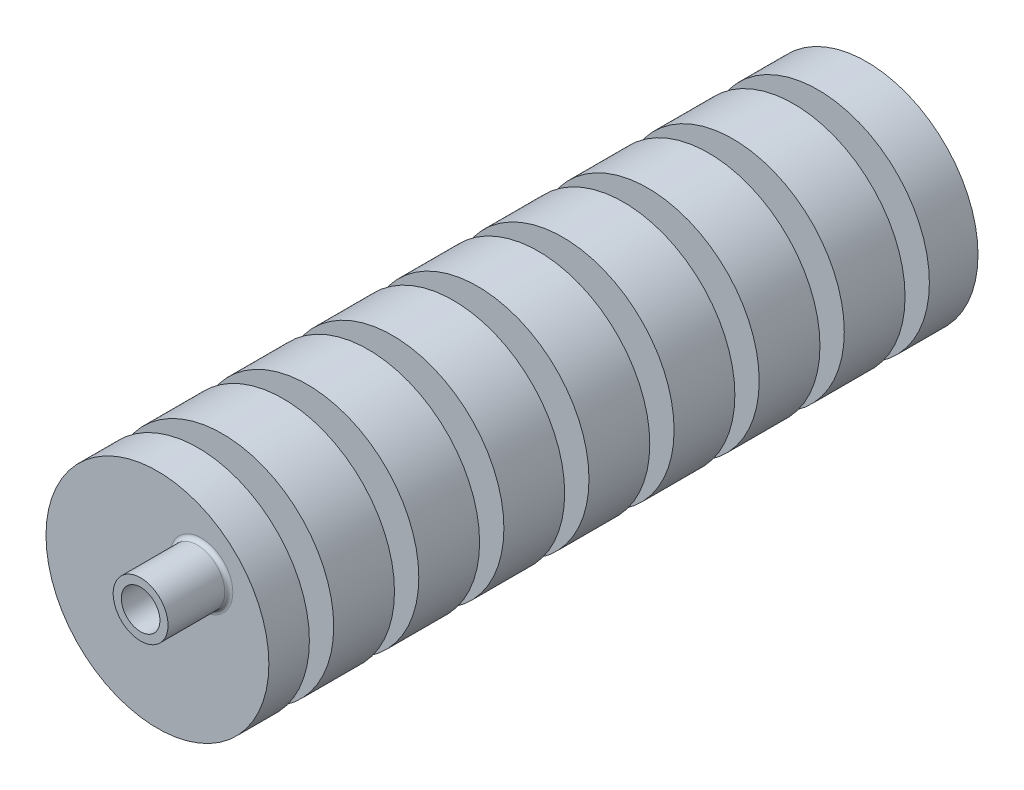
SolidWorks part; units mm, degrees
material "RUBBER 65A"
ref_plane "Front Plane" through (0, 0, 0) normal (0, 0, 1) x (1, 0, 0)
ref_plane "Top Plane" through (0, 0, 0) normal (0, 1, 0) x (1, 0, 0)
ref_plane "Right Plane" through (0, 0, 0) normal (1, 0, 0) x (0, 0, -1)
sketch "Sketch3" plane through (0, 0, 0) normal (0, 0, 1) x (1, 0, 0)
  circle A0 centre (0, 0) radius 27.5
  dimension "D1" = 55
extrude "Boss-Extrude2" add sketch "Sketch3" along normal blind 175
ref_axis "Axis2" through (0, 0, 174.1287) along (0, 0, -1)
sketch "Sketch5" plane through (0, 0, 175) normal (0, 0, 1) x (1, 0, 0)
  circle A0 centre (0, 0) radius 3.175
  dimension "D1" = 6.35
extrude "Cut-Extrude1" cut sketch "Sketch5" against normal through all contours A0
sketch "Sketch4" plane through (0, 0, 0) normal (0, 1, 0) x (1, 0, 0)
  line L0 (0, -175) -> (0, 0) construction
  line L1 (-27.5, -175) -> (27.5, -175) construction
  line L3 (-27.5, -165) -> (-11.5, -165)
  line L4 (-27.5, -165) -> (-27.5, -159)
  line L5 (-27.5, -159) -> (-11.5, -159)
  line L6 (-11.5, -165) -> (-11.5, -159)
  line L63 (-27.5, -144) -> (-27.5, -138)
  line L64 (-27.5, -144) -> (-11.5, -144)
  line L65 (-11.5, -144) -> (-11.5, -138)
  line L66 (-27.5, -138) -> (-11.5, -138)
  line L67 (-27.5, -123) -> (-27.5, -117)
  line L68 (-27.5, -123) -> (-11.5, -123)
  line L69 (-11.5, -123) -> (-11.5, -117)
  line L70 (-27.5, -117) -> (-11.5, -117)
  line L71 (-27.5, -102) -> (-27.5, -96)
  line L72 (-27.5, -102) -> (-11.5, -102)
  line L73 (-11.5, -102) -> (-11.5, -96)
  line L74 (-27.5, -96) -> (-11.5, -96)
  line L75 (-27.5, -81) -> (-27.5, -75)
  line L76 (-27.5, -81) -> (-11.5, -81)
  line L77 (-11.5, -81) -> (-11.5, -75)
  line L78 (-27.5, -75) -> (-11.5, -75)
  line L79 (-27.5, -60) -> (-27.5, -54)
  line L80 (-27.5, -60) -> (-11.5, -60)
  line L81 (-11.5, -60) -> (-11.5, -54)
  line L82 (-27.5, -54) -> (-11.5, -54)
  line L83 (-27.5, -39) -> (-27.5, -33)
  line L84 (-27.5, -39) -> (-11.5, -39)
  line L85 (-11.5, -39) -> (-11.5, -33)
  line L86 (-27.5, -33) -> (-11.5, -33)
  line L87 (-27.5, -18) -> (-27.5, -12)
  line L88 (-27.5, -18) -> (-11.5, -18)
  line L89 (-11.5, -18) -> (-11.5, -12)
  line L90 (-27.5, -12) -> (-11.5, -12)
  line L91 (-27.5, -165) -> (-27.5, -144) construction
  dimension "D1" = 10
  dimension "D2" = 6
  dimension "D3" = 27.5
  dimension "D4" = 16
  dimension "D6" = 21
  dimension "D5" = 8
revolve "Cut-Revolve1" cut sketch "Sketch4" angle 360 about L0
shell "Shell1" thickness 3
sketch "Sketch10" plane through (0, 0, 0) normal (0, 0, -1) x (-1, 0, 0)
  line L0 (0, 27.5) -> (0, -27.5) construction
  line L1 (-27.5, 0) -> (27.5, 0) construction
  line L2 (-1, 27.4818) -> (-1, 3.0134)
  line L3 (1, 3.0134) -> (1, 27.4818)
  line L4 (3.0134, 1) -> (27.4818, 1)
  line L5 (3.0134, -1) -> (27.4818, -1)
  line L6 (-1, -3.0134) -> (-1, -27.4818)
  line L7 (1, -3.0134) -> (1, -27.4818)
  line L8 (-27.4818, -1) -> (-3.0134, -1)
  line L9 (-27.4818, 1) -> (-3.0134, 1)
  circle A0 centre (0, 0) radius 27.5 construction
  circle A1 centre (0, 0) radius 3.175 construction
  arc A2 (-1, -27.4818) -> (1, -27.4818) centre (0, 0) ccw
  arc A3 (27.4818, -1) -> (27.4818, 1) centre (0, 0) ccw
  arc A4 (1, 27.4818) -> (-1, 27.4818) centre (0, 0) ccw
  arc A5 (-27.4818, 1) -> (-27.4818, -1) centre (0, 0) ccw
  arc A6 (-1, -3.0134) -> (1, -3.0134) centre (0, 0) ccw
  arc A7 (-3.0134, 1) -> (-3.0134, -1) centre (0, 0) ccw
  arc A8 (1, 3.0134) -> (-1, 3.0134) centre (0, 0) ccw
  arc A9 (3.0134, -1) -> (3.0134, 1) centre (0, 0) ccw
  dimension "D1" = 1
  dimension "D2" = 1
  dimension "D3" = 1
  dimension "D4" = 1
  dimension "D5" = 1
extrude "Boss-Extrude3" add sketch "Sketch10" against normal up to surface (175 mm away) up to face at (3.175, 0, 175)
sketch "Sketch11" plane through (0, 0, 0) normal (1, 0, 0) x (0, 0, -1)
  line L0 (-117, 27.4818) -> (-117, 1) construction
  line L1 (-165, 30.0791) -> (-159, 30.0791)
  line L2 (-165, 30.0791) -> (-165, 11.4564)
  line L3 (-165, 11.4564) -> (-159, 11.4564)
  line L4 (-159, 30.0791) -> (-159, 11.4564)
  line L5 (-144, 30.0191) -> (-138, 30.0191)
  line L6 (-144, 30.0191) -> (-144, 11.4564)
  line L7 (-144, 11.4564) -> (-138, 11.4564)
  line L8 (-138, 30.0191) -> (-138, 11.4564)
  line L9 (-123, 30.1992) -> (-117, 30.1992)
  line L10 (-123, 30.1992) -> (-123, 11.4755)
  line L11 (-123, 11.4755) -> (-117, 11.4755)
  line L12 (-117, 30.1992) -> (-117, 11.4755)
  line L13 (-117, 11.4564) -> (-117, 1) construction
  line L14 (-75, 11.4564) -> (-75, 1) construction
  line L15 (-102, 30.5593) -> (-96, 30.5593)
  line L16 (-102, 30.5593) -> (-102, 11.4564)
  line L17 (-102, 11.4564) -> (-96, 11.4564)
  line L18 (-96, 30.5593) -> (-96, 11.4564)
  line L19 (-81, 30.9195) -> (-75, 30.9195)
  line L20 (-81, 30.9195) -> (-81, 11.4755)
  line L21 (-81, 11.4755) -> (-75, 11.4755)
  line L22 (-75, 30.9195) -> (-75, 11.4755)
  line L23 (-75, 27.4818) -> (-75, 1) construction
  line L25 (-60, 31.9241) -> (-54, 31.9241)
  line L26 (-60, 31.9241) -> (-60, 11.4564)
  line L27 (-60, 11.4564) -> (-54, 11.4564)
  line L28 (-54, 31.9241) -> (-54, 11.4564)
  line L29 (-39, 30.6232) -> (-33, 30.6232)
  line L30 (-39, 30.6232) -> (-39, 11.4564)
  line L31 (-39, 11.4564) -> (-33, 11.4564)
  line L32 (-33, 30.6232) -> (-33, 11.4564)
  line L33 (-18, 31.5847) -> (-12, 31.5847)
  line L34 (-18, 31.5847) -> (-18, 11.4564)
  line L35 (-18, 11.4564) -> (-12, 11.4564)
  line L36 (-12, 31.5847) -> (-12, 11.4564)
revolve "Cut-Revolve2" cut sketch "Sketch11" angle 360 about axis through (0, 0, 174.1287) along (0, 0, -1)
sketch "Sketch12" plane through (0, 0, 0) normal (0, 1, 0) x (1, 0, 0)
  line L0 (24.4796, -172) -> (6.0935, -172) construction
  line L1 (24.7296, -168) -> (23.4796, -168)
  line L2 (24.7296, -168) -> (24.7296, -172)
  line L3 (24.7296, -172) -> (23.4796, -172)
  line L4 (23.4796, -168) -> (23.4796, -172)
  line L5 (0, 0) -> (0, -175) construction
  line L6 (-3.175, -175) -> (3.175, -175) construction
  line L7 (24.4796, -156) -> (8.441, -156) construction
  line L8 (24.4796, -9) -> (8.441, -9) construction
  line L9 (24.7296, -3) -> (23.4796, -3)
  line L10 (24.7296, -3) -> (24.7296, -9)
  line L11 (24.7296, -9) -> (23.4796, -9)
  line L12 (23.4796, -3) -> (23.4796, -9)
  line L13 (24.7296, -147) -> (23.4796, -147)
  line L14 (24.7296, -147) -> (24.7296, -156)
  line L15 (24.7296, -156) -> (23.4796, -156)
  line L16 (23.4796, -147) -> (23.4796, -156)
  line L17 (24.4796, -135) -> (8.441, -135) construction
  line L18 (24.7296, -126) -> (23.4796, -126)
  line L19 (24.7296, -126) -> (24.7296, -135)
  line L20 (24.7296, -135) -> (23.4796, -135)
  line L21 (23.4796, -126) -> (23.4796, -135)
  line L22 (24.4796, -114) -> (8.441, -114) construction
  line L23 (24.7296, -105) -> (23.4796, -105)
  line L24 (24.7296, -105) -> (24.7296, -114)
  line L25 (24.7296, -114) -> (23.4796, -114)
  line L26 (23.4796, -105) -> (23.4796, -114)
  line L27 (24.4796, -93) -> (8.441, -93) construction
  line L28 (24.7296, -84) -> (23.4796, -84)
  line L29 (24.7296, -84) -> (24.7296, -93)
  line L30 (24.7296, -93) -> (23.4796, -93)
  line L31 (23.4796, -84) -> (23.4796, -93)
  line L32 (24.4796, -72) -> (8.441, -72) construction
  line L33 (24.7296, -63) -> (23.4796, -63)
  line L34 (24.7296, -63) -> (24.7296, -72)
  line L35 (24.7296, -72) -> (23.4796, -72)
  line L36 (23.4796, -63) -> (23.4796, -72)
  line L37 (24.4796, -51) -> (8.441, -51) construction
  line L38 (24.7296, -42) -> (23.4796, -42)
  line L39 (24.7296, -42) -> (24.7296, -51)
  line L40 (24.7296, -51) -> (23.4796, -51)
  line L41 (23.4796, -42) -> (23.4796, -51)
  line L42 (24.4796, -30) -> (8.441, -30) construction
  line L43 (24.7296, -21) -> (23.4796, -21)
  line L44 (24.7296, -21) -> (24.7296, -30)
  line L45 (24.7296, -30) -> (23.4796, -30)
  line L46 (23.4796, -21) -> (23.4796, -30)
  dimension "D1" = 1.25
  dimension "D2" = 1.25
  dimension "D3" = 1.25
  dimension "D4" = 1.25
  dimension "D5" = 1.25
  dimension "D6" = 1.25
  dimension "D7" = 1.25
  dimension "D8" = 1.25
  dimension "D9" = 1.25
revolve "Revolve1" add sketch "Sketch12" angle 360 about L5
ref_plane "Plane1" through (0, 0, 0) normal (-0.7071, -0.7071, 0) x (0, 0, -1)
ref_plane "Plane2" through (0, 0, 0) normal (-0.7071, 0.7071, 0) x (0, 0, -1)
sketch "Sketch13" plane through (0, 0, 175) normal (0, 0, 1) x (1, 0, 0)
  line L0 (0, 27.5) -> (0, -27.5) construction
  line L1 (27.5, 0) -> (-27.5, 0) construction
  line L2 (0, 0) -> (19.4454, 19.4454) construction
  line L3 (22.3322, 22.3322) -> (-22.3322, -22.3322) construction
  circle A0 centre (10.8453, 10.8453) radius 6.7625
  circle A1 centre (10.8453, 10.8453) radius 4.7625
  circle A2 centre (0, 0) radius 15.3375 construction
  circle A3 centre (0, 0) radius 27.5 construction
  dimension "D1" = 2
  dimension "D2" = 9.525
  dimension "D3" = 30.675
extrude "Boss-Extrude4" add sketch "Sketch13" along normal blind 15
sketch "Sketch14" plane through (0, 0, 190) normal (0, 0, 1) x (1, 0, 0)
  circle A0 centre (10.8453, 10.8453) radius 4.7625
  dimension "D1" = 9.525
extrude "Cut-Extrude2" cut sketch "Sketch14" against normal blind 18
fillet "Fillet1" radius 1 1 edges at (17.6078, 10.8453, 175)
equation "\"inwall\"= .75"
equation "\"outwall\"=2"
